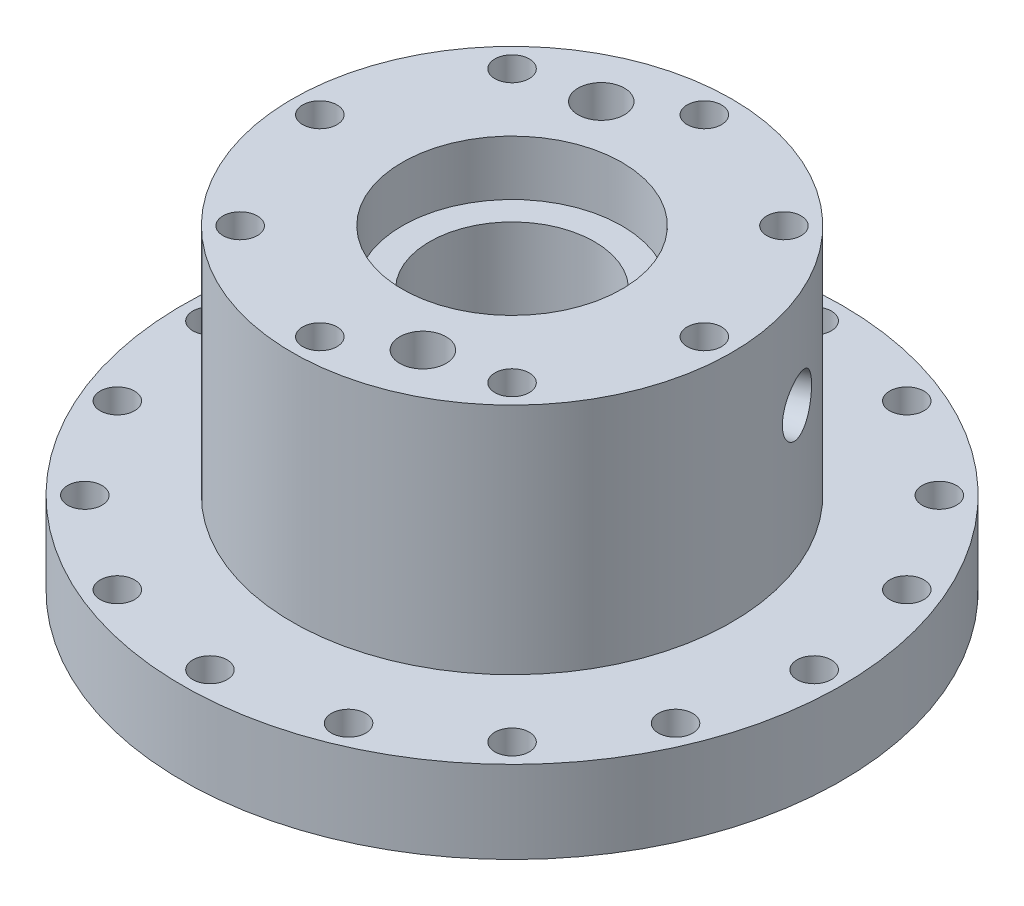
SolidWorks part; units mm, degrees
material "6061-T4 (SS)"
ref_plane "Front Plane" through (0, 0, 0) normal (0, 0, 1) x (1, 0, 0)
ref_plane "Top Plane" through (0, 0, 0) normal (0, 1, 0) x (1, 0, 0)
ref_plane "Right Plane" through (0, 0, 0) normal (1, 0, 0) x (0, 0, -1)
sketch "Sketch1" plane through (0, 0, 0) normal (0, 0, 1) x (1, 0, 0)
  line L0 (-76.2, 19.05) -> (-76.2, 0)
  line L1 (-76.2, 0) -> (-42.8625, 0)
  line L3 (-50.8, 19.05) -> (-76.2, 19.05)
  line L9 (-42.8625, 0) -> (-25.4, 15.875)
  line L10 (-25.4, 15.875) -> (-19.05, 15.875)
  line L11 (-19.05, 15.875) -> (-19.05, 60.325)
  line L12 (-19.05, 60.325) -> (-25.4, 60.325)
  line L13 (-25.4, 60.325) -> (-25.4, 73.025)
  line L14 (-25.4, 73.025) -> (-50.8, 73.025)
  line L15 (-50.8, 73.025) -> (-50.8, 19.05)
  line L16 (0, 0) -> (0, 51.8362) construction
  dimension "D1" = 76.2
  dimension "D2" = 19.05
  dimension "D3" = 33.3375
  dimension "D4" = 19.05
  dimension "D5" = 6.35
  dimension "D6" = 15.875
  dimension "D7" = 44.45
  dimension "D8" = 12.7
  dimension "D9" = 6.35
  dimension "D10" = 25.4
revolve "Revolve1" add sketch "Sketch1" angle 360 about L16
hole_wizard "5/16 (0.3125) Diameter Hole1" positions "Sketch4" profile "Sketch5" hole size "5/16" standard "ANSI Inch"
sketch "Sketch4" plane through (0, 19.05, 0) normal (0, 1, 0) x (1, 0, 0)
  point P0 (-69.85, 0)
  dimension "D1" = 69.85
sketch "Sketch5" plane through (-69.85, 19.05, 0) normal (1, 0, 0) x (0, 0, 1)
  line L0 (0, 0) -> (0, 40.4847)
  line L1 (0, 40.4847) -> (3.9687, 38.1)
  line L2 (3.9687, 38.1) -> (3.9687, 0)
  line L5 (3.9687, 0) -> (0, 0)
  line L10 (0, 40.4847) -> (-3.9688, 38.1) construction
  line L11 (0, -6.35) -> (0, 107.95) construction
  dimension "Hole Dia." = 7.9375
  dimension "Hole Depth" = 38.1
  dimension "Drill Angle" = 118
ref_axis "Axis1" through (0, 0.635, 0) along (0, -1, 0)
pattern_circular "CirPattern1" count 16 over 360 about axis through (0, 0.635, 0) along (0, -1, 0) of "5/16 (0.3125) Diameter Hole1"
hole_wizard "5/16 (0.3125) Diameter Hole2" positions "Sketch6" profile "Sketch7" hole size "5/16" standard "ANSI Inch"
sketch "Sketch6" plane through (0, 73.025, 0) normal (0, 1, 0) x (1, 0, 0)
  point P0 (44.45, 0)
  dimension "D1" = 44.45
sketch "Sketch7" plane through (44.45, 73.025, 0) normal (1, 0, 0) x (0, 0, 1)
  line L0 (0, 0) -> (0, 27.7847)
  line L1 (0, 27.7847) -> (3.9687, 25.4)
  line L2 (3.9687, 25.4) -> (3.9687, 0)
  line L5 (3.9687, 0) -> (0, 0)
  line L10 (0, 27.7847) -> (-3.9688, 25.4) construction
  line L11 (0, -6.35) -> (0, 107.95) construction
  dimension "Hole Dia." = 7.9375
  dimension "Hole Depth" = 25.4
  dimension "Drill Angle" = 118
pattern_circular "CirPattern2" count 8 over 360 about axis through (0, 0, 0) along (0, -1, 0) of "5/16 (0.3125) Diameter Hole2"
ref_plane "Plane1" through (46.9331, 0, -19.4403) normal (0.9239, 0, -0.3827) x (0, -1, 0)
hole_wizard "1/4 NPT Tapped Hole1" positions "Sketch8" profile "Sketch9" size "1/4" standard "ANSI Inch"
sketch "Sketch8" plane through (46.9331, 0, -19.4403) normal (0.9239, 0, -0.3827) x (0, -1, 0)
  line L0 (-73.025, 50.8) -> (-73.025, -50.8) construction
  point P0 (-50.8, 0)
  dimension "D1" = 22.225
sketch "Sketch9" plane through (46.9331, 50.8, -19.4403) normal (0, 1, 0) x (-0.3827, 0, -0.9239)
  line L0 (0, 0) -> (0, 41.4423)
  line L1 (5.5626, 38.1) -> (0, 41.4423)
  line L2 (-5.5626, 38.1) -> (0, 41.4423) construction
  line L3 (5.5626, 38.1) -> (5.5626, 9.906)
  line L4 (5.5626, 9.906) -> (5.9437, 9.906)
  line L5 (5.9437, 9.906) -> (6.2403, 0)
  line L6 (-5.9437, 9.906) -> (-6.2403, 0) construction
  line L7 (6.2403, 0) -> (0, 0)
  line L8 (0, -6.35) -> (0, 107.95) construction
  line L11 (-5.5626, 9.906) -> (-5.9437, 9.906) construction
  dimension "Tap Drill Dia." = 11.1252
  dimension "Tap Drill Depth" = 38.1
  dimension "Thread Dia." = 12.4806
  dimension "Thread Angle" = 3.43
  dimension "Thread Depth" = 9.906
  dimension "Drill Angle" = 118
cosmetic thread "Hole Thread1" parameters "D1"=9.906, "D2"=13.7086
hole_wizard "Tap Drill for 1/2-13 Tap1" positions "Sketch12" profile "Sketch13" hole size "1/2-13" standard "ANSI Inch"
sketch "Sketch12" plane through (0, 73.025, 0) normal (0, 1, 0) x (1, 0, 0)
  line L0 (0, 33.8578) -> (0, 0) construction
  line L1 (0, 0) -> (-14.5802, 35.1998) construction
  point P0 (-14.5802, 35.1998)
  dimension "D1" = 22.5
  dimension "D2" = 38.1
sketch "Sketch13" plane through (-14.5802, 73.025, -35.1998) normal (1, 0, 0) x (0, 0, 1)
  line L0 (0, 0) -> (0, 66.7195)
  line L1 (0, 66.7195) -> (5.3581, 63.5)
  line L2 (5.3581, 63.5) -> (5.3581, 0)
  line L5 (5.3581, 0) -> (0, 0)
  line L10 (0, 66.7195) -> (-5.3581, 63.5) construction
  line L11 (0, -6.35) -> (0, 107.95) construction
  dimension "Hole Dia." = 10.7163
  dimension "Hole Depth" = 63.5
  dimension "Drill Angle" = 118
pattern_circular "CirPattern3" count 2 over 360 about axis through (0, 0, 0) along (0, -1, 0) of "Tap Drill for 1/2-13 Tap1"
